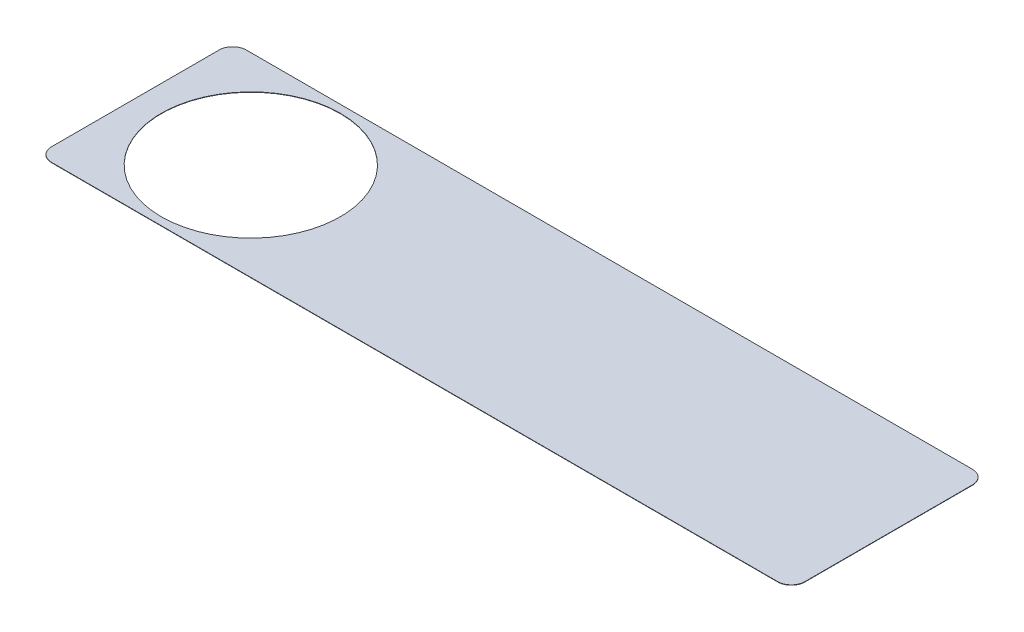
SolidWorks part; units mm, degrees
ref_plane "Front Plane" through (0, 0, 0) normal (0, 0, 1) x (1, 0, 0)
ref_plane "Top Plane" through (0, 0, 0) normal (0, 1, 0) x (1, 0, 0)
ref_plane "Right Plane" through (0, 0, 0) normal (1, 0, 0) x (0, 0, -1)
sketch "Sketch1" plane through (0, 0, 0) normal (0, 1, 0) x (1, 0, 0)
  line L24 (-76.7058, 6.6283) -> (-76.7058, -41.4914)
  line L25 (-72.8058, -45.3914) -> (135.7798, -45.3914)
  line L26 (139.6798, -41.4914) -> (139.6798, 6.6283)
  line L27 (135.7798, 10.5283) -> (-72.8058, 10.5283)
  line L28 (-76.7058, 6.6283) -> (-76.7058, -41.4914)
  line L29 (-72.8058, -45.3914) -> (135.7798, -45.3914)
  line L30 (139.6798, -41.4914) -> (139.6798, 6.6283)
  line L31 (135.7798, 10.5283) -> (-72.8058, 10.5283)
  circle A8 centre (-43.538, -17.4315) radius 25.7363
  arc A21 (-72.8058, 10.5283) -> (-76.7058, 6.6283) centre (-72.8058, 6.6283) ccw
  arc A22 (-76.7058, -41.4914) -> (-72.8058, -45.3914) centre (-72.8058, -41.4914) ccw
  arc A23 (135.7798, -45.3914) -> (139.6798, -41.4914) centre (135.7798, -41.4914) ccw
  arc A24 (139.6798, 6.6283) -> (135.7798, 10.5283) centre (135.7798, 6.6283) ccw
  arc A25 (-72.8058, 10.5283) -> (-76.7058, 6.6283) centre (-72.8058, 6.6283) ccw
  arc A26 (-76.7058, -41.4914) -> (-72.8058, -45.3914) centre (-72.8058, -41.4914) ccw
  arc A27 (135.7798, -45.3914) -> (139.6798, -41.4914) centre (135.7798, -41.4914) ccw
  arc A28 (139.6798, 6.6283) -> (135.7798, 10.5283) centre (135.7798, 6.6283) ccw
  circle A41 centre (-43.538, -17.4315) radius 25.7363 construction
  dimension "D1" = 0.1
extrude "Boss-Extrude1" add sketch "Sketch1" along normal blind 0.1
